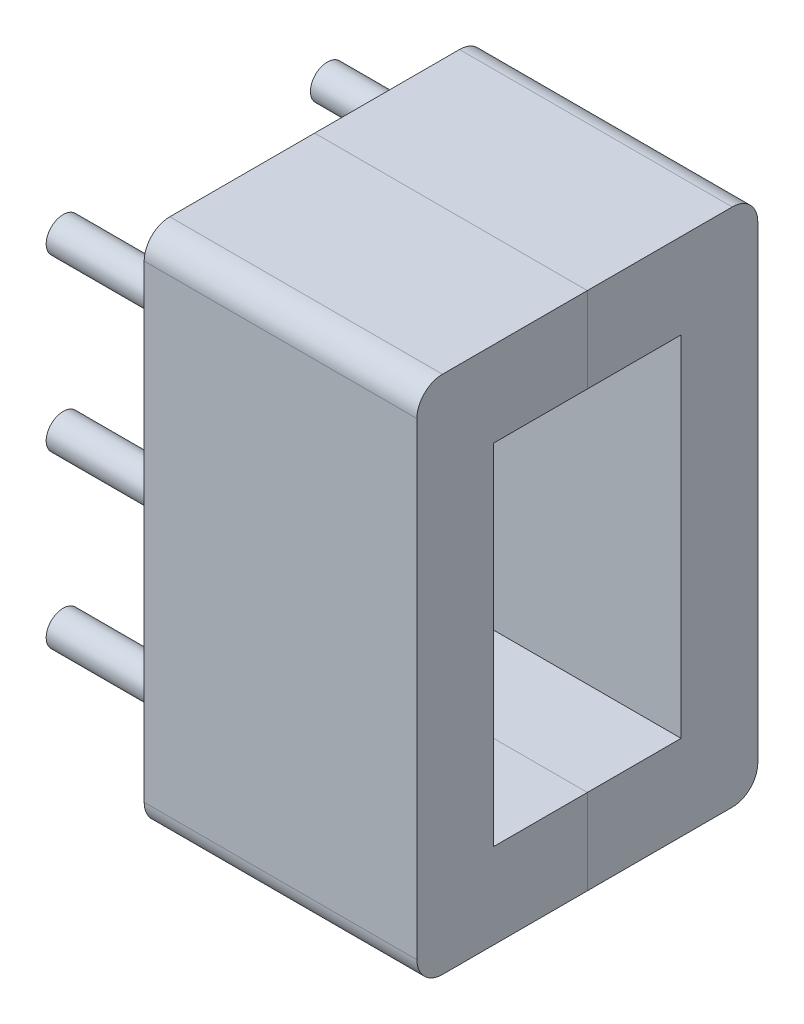
SolidWorks part; units mm, degrees
ref_plane "Alzado" through (0, 0, 0) normal (0, 0, 1) x (1, 0, 0)
ref_plane "Planta" through (0, 0, 0) normal (0, 1, 0) x (1, 0, 0)
ref_plane "Vista lateral" through (0, 0, 0) normal (1, 0, 0) x (0, 0, -1)
sketch "Croquis2" plane through (0, 0, 0) normal (1, 0, 0) x (0, 0, -1)
  line L0 (0, 24.489) -> (0, -53.3578) construction
  line L1 (5.835, 13.2874) -> (5.835, 12.9749) construction
  line L2 (10, 6.2874) -> (10, 3.7874) construction
  line L3 (5.835, -38.7126) -> (5.835, -38.4002) construction
  line L4 (5.835, -38.7126) -> (8, -38.7126) construction
  line L5 (9, -32.7126) -> (9, -37.7126) construction
  line L6 (10, -29.2126) -> (10, -31.7126) construction
  line L7 (5.835, 13.2874) -> (8, 13.2874) construction
  line L8 (9, 7.2874) -> (9, 12.2874) construction
  line L9 (6.5, 7.2874) -> (-6.5, 7.2874) construction
  line L10 (10, -29.2126) -> (10, 3.7874) construction
  line L11 (5.835, 13.2874) -> (5.835, 12.9749) construction
  line L12 (10, 6.2874) -> (10, 3.7874) construction
  line L13 (5.835, -38.7126) -> (5.835, -38.4002) construction
  line L14 (5.835, -38.7126) -> (8, -38.7126) construction
  line L15 (9, -32.7126) -> (9, -37.7126) construction
  line L16 (10, -29.2126) -> (10, -31.7126) construction
  line L17 (5.835, 13.2874) -> (8, 13.2874) construction
  line L18 (9, 7.2874) -> (9, 12.2874) construction
  line L19 (6.5, 7.2874) -> (-6.5, 7.2874) construction
  line L20 (10, -29.2126) -> (10, 3.7874) construction
  line L21 (-20, 17.7874) -> (20, 17.7874)
  line L22 (20, 17.7874) -> (20, -43.2126)
  line L24 (20, -43.2126) -> (-20, -43.2126)
  line L25 (-20, 17.7874) -> (-20, -43.2126)
  line L26 (-6.5, -32.7126) -> (6.5, -32.7126) construction
  line L27 (9, -32.7126) -> (6.5, -32.7126) construction
  line L28 (-6.5, -32.7126) -> (6.5, -32.7126) construction
  line L29 (9, -32.7126) -> (6.5, -32.7126) construction
  line L30 (-3, -33.7126) -> (-3, -32.7126) construction
  line L31 (3, -33.7126) -> (3, -32.7126) construction
  line L32 (-3, -33.7126) -> (-3, -32.7126) construction
  line L33 (3, -33.7126) -> (3, -32.7126) construction
  arc A0 (5.835, -38.4002) -> (4.335, -38.4002) centre (5.085, -36.3426) ccw construction
  arc A1 (4.335, 12.9749) -> (5.835, 12.9749) centre (5.085, 10.9174) ccw construction
  arc A2 (5.835, -38.4002) -> (4.335, -38.4002) centre (5.085, -36.3426) ccw construction
  arc A3 (4.335, 12.9749) -> (5.835, 12.9749) centre (5.085, 10.9174) ccw construction
  arc A4 (8, -38.7126) -> (9, -37.7126) centre (8, -37.7126) ccw construction
  arc A5 (9, -32.7126) -> (10, -31.7126) centre (9, -31.7126) ccw construction
  arc A6 (9, 12.2874) -> (8, 13.2874) centre (8, 12.2874) ccw construction
  arc A7 (10, 6.2874) -> (9, 7.2874) centre (9, 6.2874) ccw construction
  arc A8 (8, -38.7126) -> (9, -37.7126) centre (8, -37.7126) ccw construction
  arc A9 (9, -32.7126) -> (10, -31.7126) centre (9, -31.7126) ccw construction
  arc A10 (9, 12.2874) -> (8, 13.2874) centre (8, 12.2874) ccw construction
  arc A11 (10, 6.2874) -> (9, 7.2874) centre (9, 6.2874) ccw construction
  point P31 (0, -43.2126)
  point P33 (0, 17.7874)
  dimension "D1" = 4.5
  dimension "D2" = 10
  dimension "D3" = 4.5
extrude "Saliente-Extruir1" add sketch "Croquis2" against normal blind 32
sketch "Croquis4" plane through (0, 0, 0) normal (1, 0, 0) x (0, 0, -1)
  line L0 (3, -33.7126) -> (3, -32.7126) construction
  line L1 (-6.5, -32.7126) -> (6.5, -32.7126) construction
  line L2 (9, -32.7126) -> (6.5, -32.7126) construction
  line L3 (10, -29.2126) -> (10, -31.7126) construction
  line L4 (10, 6.2874) -> (10, 3.7874) construction
  line L5 (10, -29.2126) -> (10, 3.7874) construction
  line L6 (6.5, 7.2874) -> (-6.5, 7.2874) construction
  line L7 (0, 24.489) -> (0, -53.3578) construction
  line L8 (3, -33.7126) -> (3, -32.7126) construction
  line L9 (-6.5, -32.7126) -> (6.5, -32.7126) construction
  line L10 (9, -32.7126) -> (6.5, -32.7126) construction
  line L11 (10, -29.2126) -> (10, -31.7126) construction
  line L12 (10, 6.2874) -> (10, 3.7874) construction
  line L13 (10, -29.2126) -> (10, 3.7874) construction
  line L14 (6.5, 7.2874) -> (-6.5, 7.2874) construction
  line L15 (0, 24.489) -> (0, -53.3578) construction
  line L16 (-11, 7.7874) -> (11, 7.7874)
  line L17 (11, 7.7874) -> (11, -33.2126)
  line L19 (-11, 7.7874) -> (-11, -33.2126)
  line L35 (3, -33.7126) -> (2.5, -34.2126) construction
  line L43 (11, -33.2126) -> (-11, -33.2126)
  arc A0 (9, -32.7126) -> (10, -31.7126) centre (9, -31.7126) ccw construction
  arc A1 (9, -32.7126) -> (10, -31.7126) centre (9, -31.7126) ccw construction
  point P14 (0, -33.2126)
  point P20 (0, 7.7874)
  point P22 (0, -43.2126)
  dimension "D1" = 0.5
  dimension "D2" = 1
  dimension "D3" = 0.5
  dimension "D8" = 0.5
  dimension "D9" = 2.5
extrude "Cortar-Extruir1" cut sketch "Croquis4" against normal through all both and the other way through all
sketch "Croquis5" plane through (-32, 0, 0) normal (-1, 0, 0) x (0, 0, 1)
  line L0 (-9, 7.2874) -> (-9, 12.2874) construction
  line L1 (-9, -32.7126) -> (-9, -37.7126) construction
  line L2 (-5.835, -38.7126) -> (-8, -38.7126) construction
  line L3 (-5.835, 13.2874) -> (-8, 13.2874) construction
  line L4 (-9, 7.2874) -> (-9, 12.2874) construction
  line L5 (-9, -32.7126) -> (-9, -37.7126) construction
  line L6 (-5.835, -38.7126) -> (-8, -38.7126) construction
  line L7 (-5.835, 13.2874) -> (-8, 13.2874) construction
  line L8 (0, 24.489) -> (0, -53.3578) construction
  line L9 (0, 24.489) -> (0, -53.3578) construction
  line L10 (9.5, 13.7874) -> (-9.5, 13.7874)
  line L11 (-9.5, 13.7874) -> (-9.5, -39.2126)
  line L12 (-9.5, -39.2126) -> (9.5, -39.2126)
  line L13 (9.5, 13.7874) -> (9.5, -39.2126)
  arc A0 (-4.335, -38.4002) -> (-5.835, -38.4002) centre (-5.085, -36.3426) ccw construction
  arc A1 (-5.835, 12.9749) -> (-4.335, 12.9749) centre (-5.085, 10.9174) ccw construction
  arc A2 (-4.335, -38.4002) -> (-5.835, -38.4002) centre (-5.085, -36.3426) ccw construction
  arc A3 (-5.835, 12.9749) -> (-4.335, 12.9749) centre (-5.085, 10.9174) ccw construction
  point P21 (0, -39.2126)
  point P22 (0, 13.7874)
  dimension "D1" = 0.5
  dimension "D2" = 0.5
  dimension "D3" = 0.5
extrude "Cortar-Extruir2" cut sketch "Croquis5" against normal blind 8 and the other way through all
sketch "Croquis7" plane through (-24, 0, 0) normal (-1, 0, 0) x (0, 0, 1)
  line L4 (-9.5, 7.7874) -> (9.5, 7.7874)
  line L5 (9.5, 7.7874) -> (9.5, 13.7874)
  line L6 (9.5, 13.7874) -> (-9.5, 13.7874)
  line L7 (-9.5, 13.7874) -> (-9.5, 7.7874)
  line L8 (-9.5, 7.7874) -> (9.5, 7.7874)
  line L9 (9.5, 7.7874) -> (9.5, 13.7874)
  line L10 (9.5, 13.7874) -> (-9.5, 13.7874)
  line L11 (-9.5, 13.7874) -> (-9.5, 7.7874)
  line L12 (9.5, -33.2126) -> (-9.5, -33.2126)
  line L13 (-9.5, -33.2126) -> (-9.5, -39.2126)
  line L14 (-9.5, -39.2126) -> (9.5, -39.2126)
  line L15 (9.5, -39.2126) -> (9.5, -33.2126)
  line L16 (9.5, -33.2126) -> (-9.5, -33.2126)
  line L17 (-9.5, -33.2126) -> (-9.5, -39.2126)
  line L18 (-9.5, -39.2126) -> (9.5, -39.2126)
  line L19 (9.5, -39.2126) -> (9.5, -33.2126)
  dimension "D1" = 0
  dimension "D2" = 0
extrude "Saliente-Extruir2" add sketch "Croquis7" along normal up to surface (8 mm away) from offset 2.5 up to face at (-32, -12.7126, 0)
sketch "Croquis9" plane through (-32, 0, 0) normal (1, 0, 0) x (0, 0, -1)
  line L0 (-15.5, 3.7699) -> (-15.5, -40.0796) construction
  line L2 (100, 3.7699) -> (-100, 3.7699) construction
  line L3 (100, 12.7699) -> (-100, 12.7699) construction
  line L4 (-20, 17.7874) -> (-20, -43.2126) construction
  line L5 (-11, -33.2126) -> (-11, 7.7874) construction
  line L6 (-20, 17.7874) -> (-20, -43.2126) construction
  line L7 (-11, -33.2126) -> (-11, 7.7874) construction
  line L8 (0, 24.489) -> (0, -53.3578) construction
  line L9 (0, 24.489) -> (0, -53.3578) construction
  line L10 (-20, 6.2236) -> (-11, 6.2236) construction
  line L11 (-15.5, 3.7699) -> (-15.5, 12.7699) construction
  circle A0 centre (-15.5, 8.2699) radius 2
  circle A1 centre (-15.5, -31.7301) radius 2
  circle A2 centre (-15.5, -11.7301) radius 2
  circle A3 centre (15.5, -31.7301) radius 2
  circle A4 centre (15.5, -11.7301) radius 2
  circle A5 centre (15.5, 8.2699) radius 2
  point P14 (-15.5, 6.2236)
  dimension "D1" = 40
  dimension "D2" = 20
  dimension "D3" = 4
extrude "Saliente-Extruir3" add sketch "Croquis9" against normal blind 14
fillet "Redondeo1" radius 3 4 edges at (-16, -43.2126, 20) (-16, -43.2126, -20) (-16, 17.7874, -20) (-16, 17.7874, 20)
sketch "Croquis10" plane through (0, 0, 20) normal (0, 0, 1) x (1, 0, 0)
  line L0 (0, 14.7874) -> (-32, 14.7874) construction
  line L1 (0, 14.7874) -> (-32, 14.7874) construction
split "Partir1" trim tools "Alzado" bodies to split 108 resulting bodies 106 107
